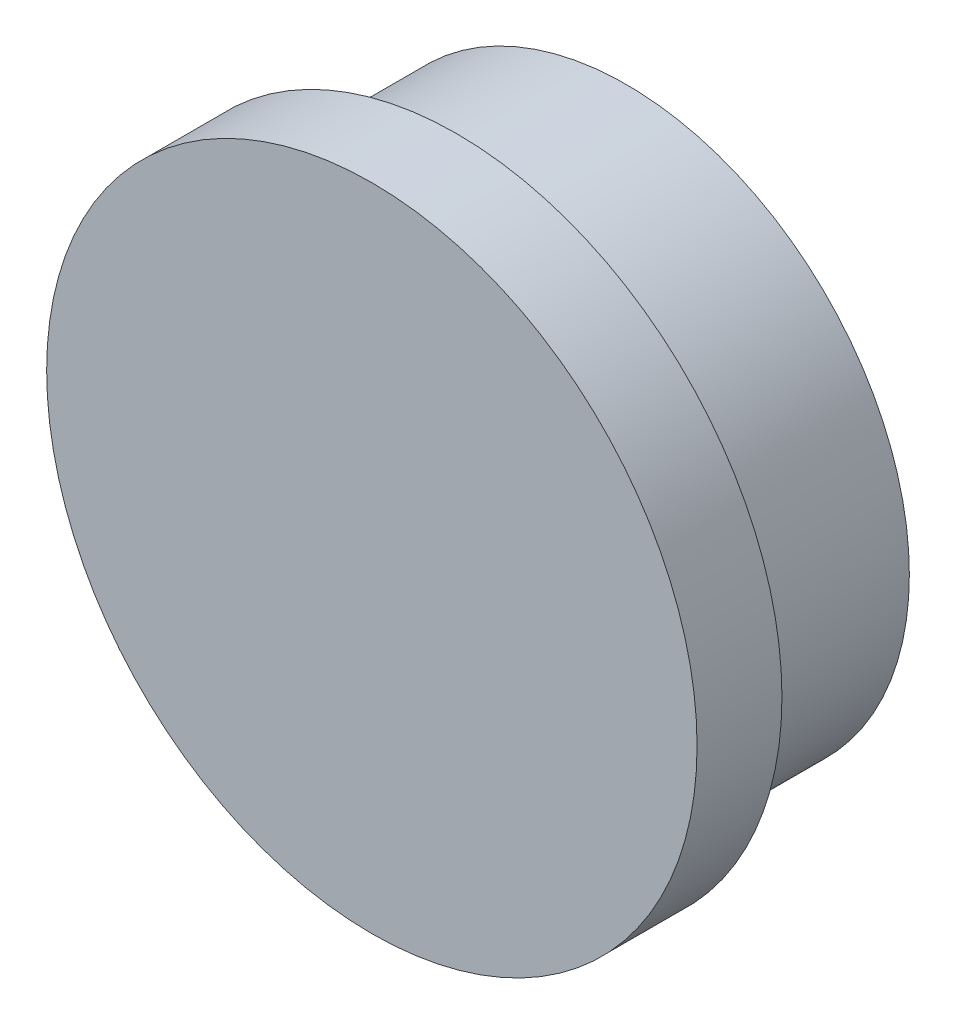
SolidWorks part; units mm, degrees
ref_plane "Front Plane" through (0, 0, 0) normal (0, 0, 1) x (1, 0, 0)
ref_plane "Top Plane" through (0, 0, 0) normal (0, 1, 0) x (1, 0, 0)
ref_plane "Right Plane" through (0, 0, 0) normal (1, 0, 0) x (0, 0, -1)
sketch "Sketch1" plane through (0, 0, 0) normal (0, 0, 1) x (1, 0, 0)
  circle A0 centre (-127.9925, 40.1033) radius 11.4962
extrude "Boss-Extrude1" add sketch "Sketch1" along normal blind 3
sketch "Sketch2" plane through (0, 0, 0) normal (0, 0, -1) x (-1, 0, 0)
  circle A0 centre (127.9925, 40.1033) radius 10 construction
  circle A1 centre (127.9925, 40.1033) radius 10
extrude "Boss-Extrude2" add sketch "Sketch2" along normal blind 6
sketch "Sketch3" plane through (0, 0, -6) normal (0, 0, -1) x (-1, 0, 0)
  circle A1 centre (127.9925, 40.1033) radius 1.5
extrude "Cut-Extrude1" cut sketch "Sketch3" against normal blind 5
